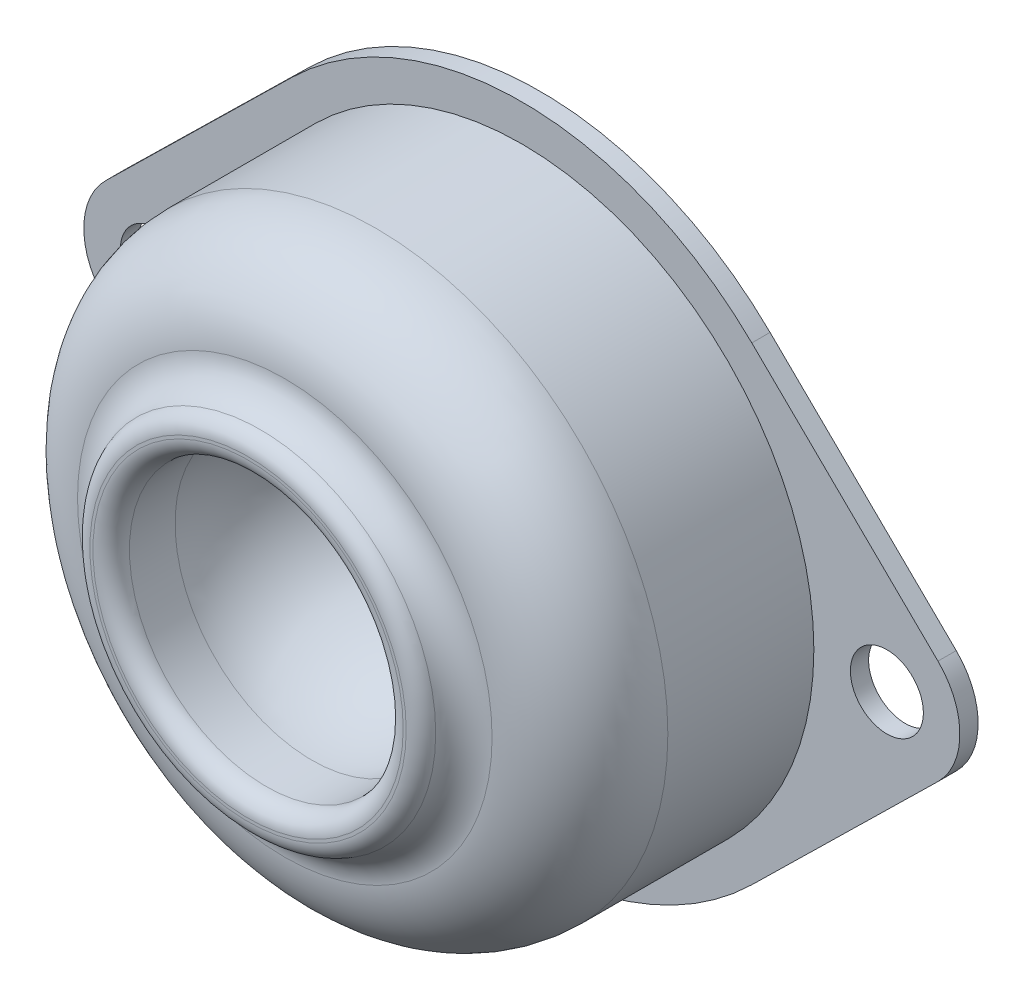
SolidWorks part; units mm, degrees
ref_plane "Front Plane" through (0, 0, 0) normal (0, 0, 1) x (1, 0, 0)
ref_plane "Top Plane" through (0, 0, 0) normal (0, 1, 0) x (1, 0, 0)
ref_plane "Right Plane" through (0, 0, 0) normal (1, 0, 0) x (0, 0, -1)
sketch "Sketch1" plane through (0, 0, 0) normal (0, 0, 1) x (1, 0, 0)
  line L0 (-23.6536, 0) -> (21.1338, 0) construction
  line L1 (0, 18.8985) -> (0, -18.7359) construction
  line L2 (-22.8, 2.8566) -> (-12.6, 12.8546)
  line L3 (-22.8, -2.8566) -> (-12.6, -12.8546)
  line L4 (11.8085, 13.6304) -> (22.8, 2.8566)
  line L5 (12.6, -12.8546) -> (22.8, -2.8566)
  circle A0 centre (-20, 0) radius 2
  circle A1 centre (20, 0) radius 2
  arc A2 (-22.8, 2.8566) -> (-22.8, -2.8566) centre (-20, 0) ccw
  arc A3 (22.8, -2.8566) -> (22.8, 2.8566) centre (20, 0) ccw
  arc A5 (-12.6, -12.8546) -> (12.6, -12.8546) centre (0, 0) ccw
  circle A6 centre (-20, 0) radius 4 construction
  arc A7 (12.6, 12.8546) -> (-12.6, 12.8546) centre (0, 0) ccw
  circle A8 centre (20, 0) radius 4 construction
  dimension "D1" = 4
  dimension "D2" = 4
  dimension "D3" = 20
  dimension "D4" = 20
  dimension "D5" = 2
  dimension "D8" = 36
  dimension "D6" = 2
extrude "Boss-Extrude1" add sketch "Sketch1" along normal blind 1 contours L4 A7 L2 A2 L3 A5 L5 A3 A0 A1 region at (0, 0, 0)
sketch "Sketch2" plane through (0, 0, 1) normal (0, 0, 1) x (1, 0, 0)
  circle A0 centre (0, 0) radius 16
  dimension "D1" = 32
extrude "Boss-Extrude2" add sketch "Sketch2" along normal blind 13
sketch "Sketch3" plane through (0, 0, 14) normal (0, 0, 1) x (1, 0, 0)
  circle A0 centre (0, 0) radius 9.5
  dimension "D1" = 19
extrude "Boss-Extrude3" add sketch "Sketch3" along normal blind 2
fillet "Fillet1" radius 5 1 edges at (16, 0, 14)
fillet "Fillet2" radius 2 1 edges at (9.5, 0, 14)
sketch "Sketch4" plane through (0, 0, 16) normal (0, 0, 1) x (1, 0, 0)
  circle A0 centre (0, 0) radius 7.5
  dimension "D1" = 15
extrude "Cut-Extrude1" cut sketch "Sketch4" against normal blind 11
fillet "Fillet3" radius 7.5 1 edges at (7.5, 0, 5)
fillet "Fillet4" radius 1 1 edges at (9.5, 0, 16)
fillet "Fillet5" radius 1 1 edges at (7.5, 0, 16)
